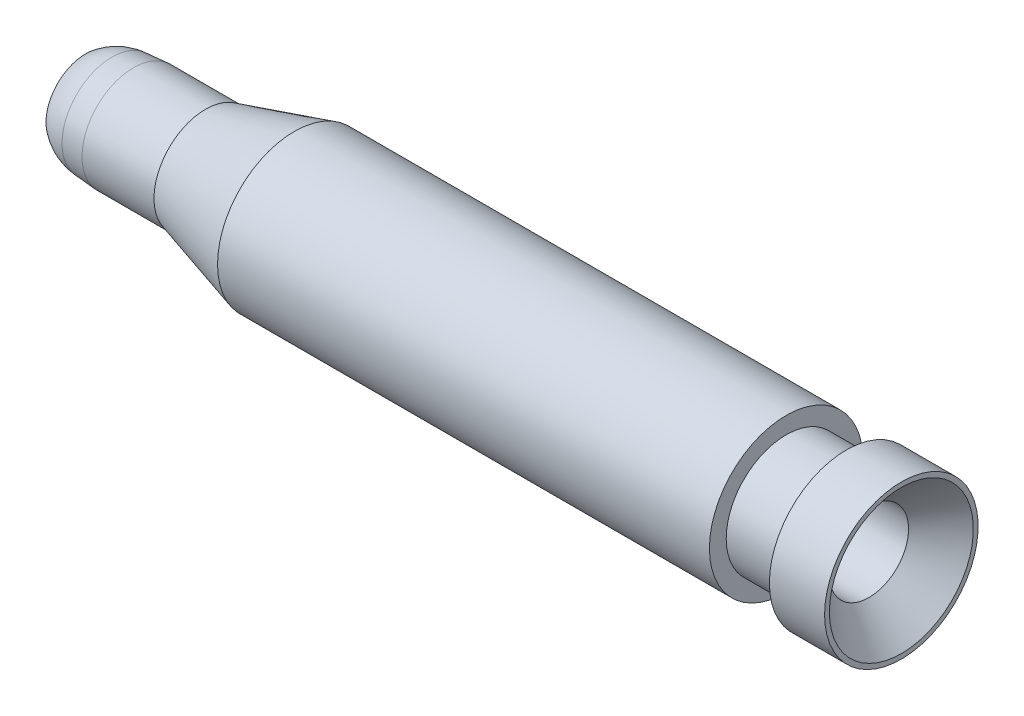
SolidWorks part; units mm, degrees
ref_plane "Plano frontal" through (0, 0, 0) normal (0, 0, 1) x (1, 0, 0)
ref_plane "Plano superior" through (0, 0, 0) normal (0, 1, 0) x (1, 0, 0)
ref_plane "Plano direito" through (0, 0, 0) normal (1, 0, 0) x (0, 0, -1)
sketch "Esboço1" plane through (0, 0, 0) normal (0, 0, 1) x (1, 0, 0)
  line L0 (0, 3.3) -> (0, 4)
  line L1 (0, 4) -> (4, 4.3)
  line L2 (4, 4.3) -> (10, 4.3)
  line L3 (10, 4.3) -> (17.4, 6.4)
  line L4 (17.4, 6.4) -> (58.4, 6.4)
  line L5 (58.4, 6.4) -> (58.4, 5)
  line L6 (58.4, 5) -> (63.4, 5)
  line L7 (63.4, 5) -> (63.4, 6.4)
  line L8 (63.4, 6.4) -> (68, 6.4)
  line L9 (68, 6.4) -> (68, 3.3)
  line L10 (68, 3.3) -> (0, 3.3)
  line L11 (0, 0) -> (86.87, 0) construction
  point P2 (37.9, 6.4)
  point P12 (65.7, 6.4)
  dimension "D1" = 0.7
  dimension "D2" = 1
  dimension "D3" = 4
  dimension "D4" = 6
  dimension "D5" = 3.1
  dimension "D6" = 7.4
  dimension "D7" = 4.6
  dimension "D8" = 5
  dimension "D9" = 68
  dimension "D10" = 41
  dimension "D11" = 3.3
  dimension "D12" = 1.4
  dimension "D13" = 6.4
revolve "Revolução1" add sketch "Esboço1" angle 360 about L11
fillet "Filete3" radius 4 1 edges at (0, 0, 4)
chamfer "Chanfro7" distance 2.7 angle 45 1 edges at (68, 0, 3.3)
